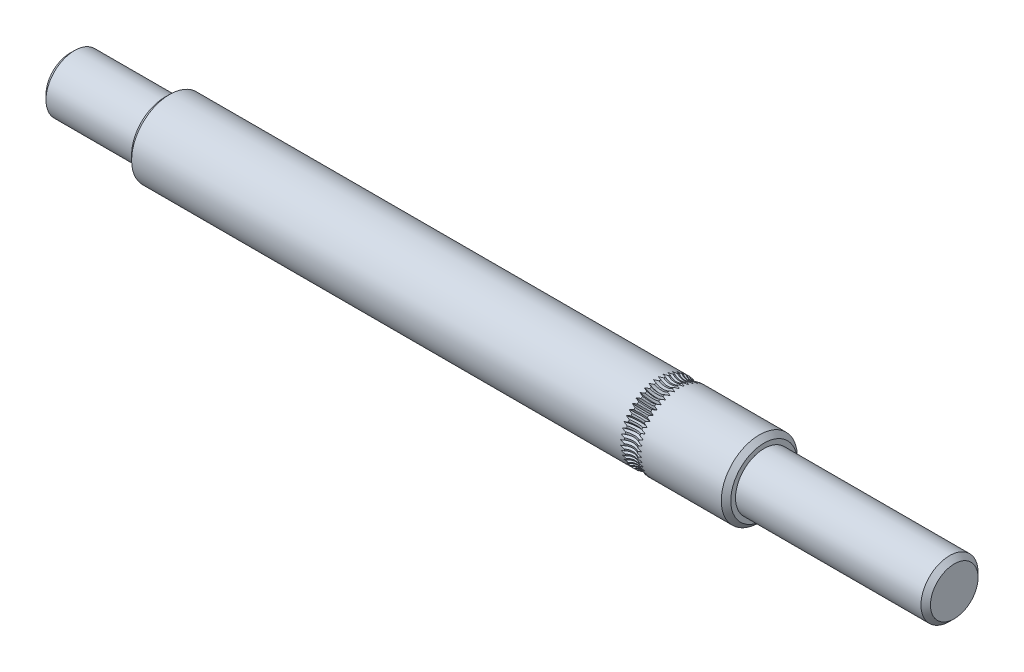
SolidWorks part; units mm, degrees
material "Plain Carbon Steel"
ref_plane "Front Plane" through (0, 0, 0) normal (0, 0, 1) x (1, 0, 0)
ref_plane "Top Plane" through (0, 0, 0) normal (0, 1, 0) x (1, 0, 0)
ref_plane "Right Plane" through (0, 0, 0) normal (1, 0, 0) x (0, 0, -1)
sketch "Sketch1" plane through (0, 0, 0) normal (0, 0, 1) x (1, 0, 0)
  line L0 (-53, 4) -> (10, 4)
  line L1 (-53, 3) -> (-63, 3)
  line L2 (-63, 0) -> (30, 0)
  line L3 (-53, 3) -> (-53, 4)
  line L4 (-63, 3) -> (-63, 0)
  line L5 (30, 0) -> (30, 3)
  line L6 (10, 4) -> (10, 3)
  line L7 (10, 3) -> (30, 3)
  line L8 (0, 0) -> (67.2135, 0) construction
  line L9 (0, 0) -> (0, 19.6593) construction
  dimension "D1" = 8
  dimension "D2" = 63
  dimension "D3" = 10
  dimension "D4" = 20
  dimension "D5" = 6
  dimension "D6" = 10
revolve "Revolve1" add sketch "Sketch1" angle 360 about L8
chamfer "Chamfer1" distance 0.5 angle 45 4 edges at (30, 0, 3) (10, 0, 4) (-53, 0, 4) (-63, 0, 3)
sketch "Sketch2" plane through (0, 0, 0) normal (1, 0, 0) x (0, 0, -1)
  line L0 (0, 0) -> (0, 5) construction
  line L1 (9.9899, 5) -> (-9.864, 5) construction
  line L2 (0.1562, 3.7705) -> (0, 3.5)
  line L3 (0, 3.5) -> (-0.1562, 3.7705)
  line L4 (-1.3354, 5) -> (1.3354, 5)
  line L5 (-0.1562, 3.7705) -> (-1.3354, 3.7705)
  line L6 (0.1562, 3.7705) -> (1.3354, 3.7705)
  line L7 (1.3354, 3.7705) -> (1.3354, 5)
  line L8 (-1.3354, 3.7705) -> (-1.3354, 5)
  line L9 (0, 0) -> (-6.9817, 0) construction
  line L10 (5.645, 4) -> (-5.97, 4) construction
  circle A0 centre (0, 0) radius 4 construction
  circle A1 centre (0, 0) radius 3.5 construction
  dimension "D5" = 5
  dimension "D1" = 60
  dimension "D2" = 3
  dimension "D3" = 2.459
  dimension "D4" = 1
revolve "Cut-Revolve1" cut sketch "Sketch2" angle 360 about L1
pattern_circular "CirPattern1" count 50 over 360 about axis through (0, 0, 0) along (-1, 0, 0) of "Cut-Revolve1"
sketch "Sketch3" plane through (0, 0, 0) normal (0, 0, 1) x (1, 0, 0)
  line L0 (29.5, 3) -> (10, 3) construction
  line L1 (8, 4) -> (0.75, 4)
  line L2 (8, 4) -> (8, 3)
  line L3 (8, 3) -> (0.75, 3)
  line L4 (0.75, 4) -> (0.75, 3)
  line L5 (-0.75, 4) -> (-8, 4)
  line L6 (-0.75, 4) -> (-0.75, 3)
  line L7 (-0.75, 3) -> (-8, 3)
  line L8 (-8, 4) -> (-8, 3)
  line L9 (0, 0) -> (0, 15.3026) construction
  line L10 (0, 0) -> (-13.7134, 0) construction
  line L11 (9.5, 4) -> (1.118, 4) construction
  dimension "D1" = 1.5
  dimension "D2" = 16
revolve "Cut-Revolve2" [suppressed] cut sketch "Sketch3" angle 360 about L10
